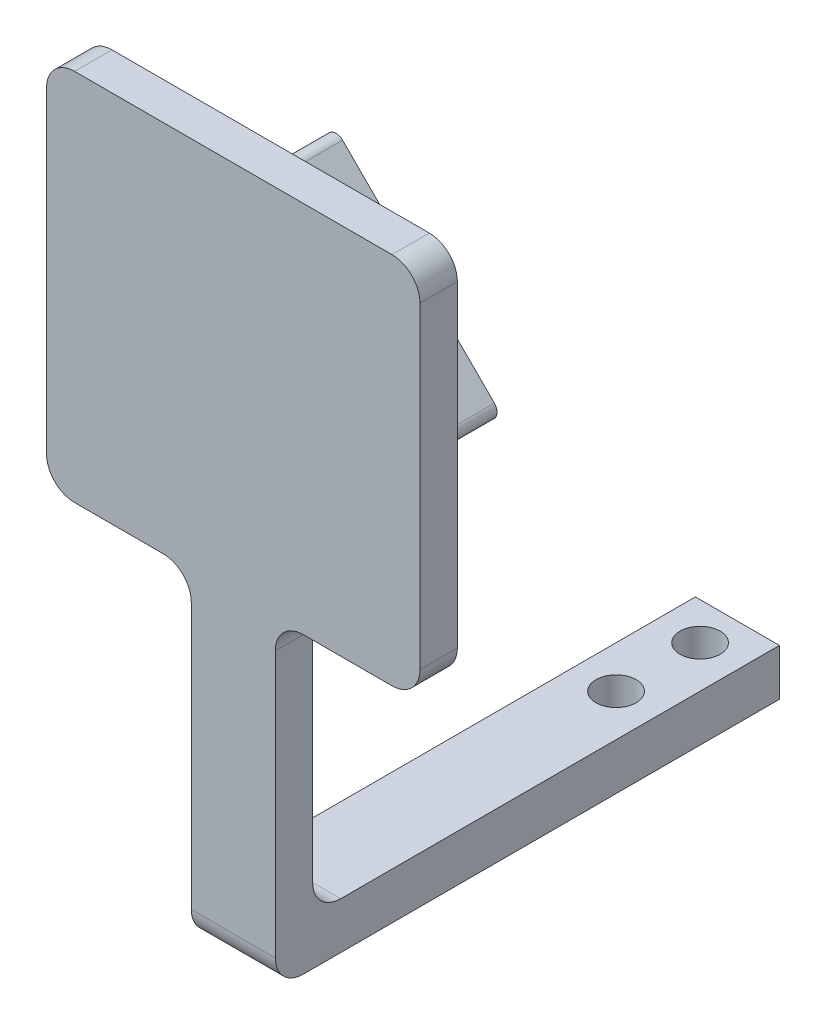
SolidWorks part; units mm, degrees
ref_plane "Front Plane" through (0, 0, 0) normal (0, 0, 1) x (1, 0, 0)
ref_plane "Top Plane" through (0, 0, 0) normal (0, 1, 0) x (1, 0, 0)
ref_plane "Right Plane" through (0, 0, 0) normal (1, 0, 0) x (0, 0, -1)
sketch "Sketch1" plane through (0, 0, 0) normal (0, 0, 1) x (1, 0, 0)
  line L0 (0, 0) -> (15.5, 0)
  line L2 (0, 0) -> (0, 40)
  line L3 (0, 40) -> (40, 40)
  line L4 (40, 0) -> (40, 40)
  line L5 (15.5, 0) -> (15.5, -34.5)
  line L6 (15.5, -34.5) -> (24.5, -34.5)
  line L7 (24.5, -34.5) -> (24.5, 0)
  line L8 (24.5, 0) -> (40, 0)
  line L9 (20, 40) -> (20, -34.5) construction
  dimension "D1" = 40
  dimension "D2" = 40
  dimension "D3" = 34.5
  dimension "D4" = 9
extrude "Boss-Extrude1" add sketch "Sketch1" along normal mid plane 4
sketch "Sketch3" plane through (0, -34.5, 0) normal (0, -1, 0) x (1, 0, 0)
  line L1 (15.5, -52) -> (24.5, -52)
  line L2 (15.5, -52) -> (15.5, -2)
  line L3 (15.5, -2) -> (24.5, -2)
  line L4 (24.5, -52) -> (24.5, -2)
  line L6 (24.5, 2) -> (24.5, -2) construction
  line L7 (15.5, -2) -> (24.5, -2) construction
  line L8 (15.5, 2) -> (15.5, -2) construction
  circle A0 centre (20, -48) radius 2.15
  circle A1 centre (20, -39) radius 2.15
  point P15 (0, 0)
  point P16 (20, -52)
  point P17 (20, -44.6041)
  dimension "D2" = 4.3
  dimension "D1" = 50
  dimension "D3" = 9
  dimension "D4" = 4
extrude "Boss-Extrude2" add sketch "Sketch3" against normal blind 5
fillet "Fillet1" radius 3 8 edges at (24.5, 0, 0) (15.5, 0, 0) (0, 0, 0) (0, 40, 0) (40, 40, 0) (40, 0, 0) (20, -34.5, 2) (20, -29.5, -2)
sketch "Sketch4" plane through (0, 0, -2) normal (0, 0, -1) x (-1, 0, 0)
  line L0 (0, 37) -> (0, 3) construction
  line L5 (-20, 2.3223) -> (-37.6777, 20)
  line L6 (-20, 2.3223) -> (-2.3223, 20)
  line L7 (-2.3223, 20) -> (-20, 37.6777)
  line L8 (-37.6777, 20) -> (-20, 37.6777)
  line L11 (-37, 40) -> (-3, 40) construction
  line L12 (-3, 0) -> (-12.5, 0) construction
  line L13 (-20, 5.1508) -> (-34.8492, 20)
  line L14 (-20, 5.1508) -> (-5.1508, 20)
  line L15 (-5.1508, 20) -> (-20, 34.8492)
  line L16 (-34.8492, 20) -> (-20, 34.8492)
  point P0 (-5.1508, 20.0152)
  point P5 (-8.5365, 32.5343)
  point P6 (0, 0)
  point P7 (-22.9334, 6.7702)
  point P8 (0, 0)
  point P9 (-14.1701, 23.55)
  point P10 (-15.8638, 23.5869)
  point P16 (-17.6312, 30.8406)
  point P19 (0, 20)
  point P22 (-20, 40)
  point P25 (-1.9519, 20.3247)
  point P26 (0, 0)
  point P27 (-22.2706, 32.0188)
  point P28 (0, 0)
  point P29 (-20.8346, 1.4207)
  point P30 (-8.1683, 18.8002)
  point P31 (0, 0)
  point P32 (0, 0)
  dimension "D1" = 25
  dimension "D2" = 25
  dimension "D3" = 2
  dimension "D4" = 2
  dimension "D5" = 45
extrude "Boss-Extrude3" add sketch "Sketch4" along normal blind 7
sketch "Sketch5" plane through (11.1612, 11.1612, 0) normal (-0.7071, -0.7071, 0) x (0, 0, 1)
  line L0 (-9, -12.5) -> (-2, -12.5) construction
  line L1 (-9, -12.5) -> (-9, 12.5) construction
  circle A0 centre (-5.5, 0) radius 2.6
  point P4 (-5.5, -12.5)
  point P7 (-9, 0)
  dimension "D1" = 5.2
extrude "Cut-Extrude1" cut sketch "Sketch5" against normal up to surface (25 mm away) up to face at (28.8388, 28.8388, -5.5)
sketch "Sketch7" plane through (8.8388, -8.8388, 0) normal (0.7071, -0.7071, 0) x (0.7071, 0.7071, 0)
  line L0 (40.7843, -9) -> (15.7843, -9) construction
  line L1 (40.7843, -9) -> (40.7843, -2) construction
  circle A0 centre (28.2843, -5.5) radius 2.6
  point P4 (28.2843, -9)
  point P7 (40.7843, -5.5)
  dimension "D1" = 5.2
extrude "Cut-Extrude2" cut sketch "Sketch7" against normal up to surface (25 mm away) up to face at (11.1612, 28.8388, -5.5)
sketch "Sketch9" plane through (0, 0, -9) normal (0, 0, -1) x (-1, 0, 0)
  line L0 (-22.8284, 5.1508) -> (-20, 2.3223)
  line L1 (-37.6777, 20) -> (-20, 2.3223) construction
  line L2 (-20, 2.3223) -> (-17.1716, 5.1508)
  line L3 (-17.1716, 5.1508) -> (-18.5858, 6.565)
  line L4 (-20, 5.1508) -> (-5.1508, 20) construction
  line L5 (-18.5858, 6.565) -> (-20, 5.1508)
  line L6 (-20, 5.1508) -> (-21.4142, 6.565)
  line L7 (-34.8492, 20) -> (-20, 5.1508) construction
  line L8 (-21.4142, 6.565) -> (-22.8284, 5.1508)
  point P5 (0, 0)
  dimension "D1" = 4
extrude "Cut-Extrude3" cut sketch "Sketch9" against normal up to surface (7 mm away) up to face at (20, 7.303, -2)
fillet "Fillet2" radius 1 10 edges at (21.4142, 6.565, -5.5) (18.5858, 6.565, -5.5) (17.1716, 5.1508, -5.5) (22.8284, 5.1508, -5.5) (5.1508, 20, -5.5) (2.3223, 20, -5.5) (20, 37.6777, -5.5) (20, 34.8492, -5.5) (34.8492, 20, -5.5) (37.6777, 20, -5.5)
